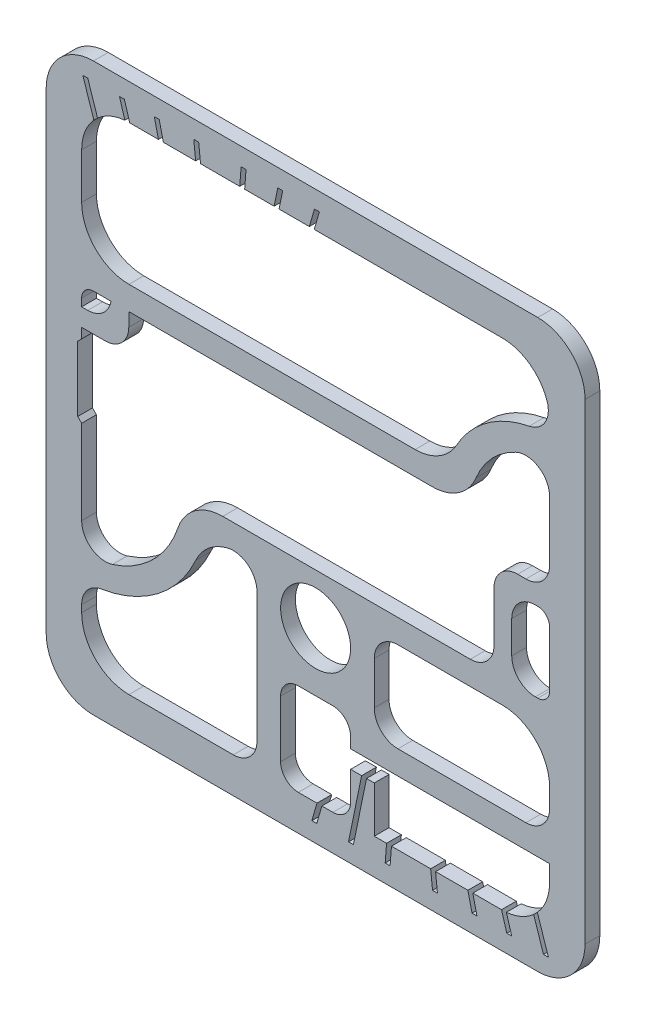
SolidWorks part; units mm, degrees
ref_plane "Front Plane" through (0, 0, 0) normal (0, 0, 1) x (1, 0, 0)
ref_plane "Top Plane" through (0, 0, 0) normal (0, 1, 0) x (1, 0, 0)
ref_plane "Right Plane" through (0, 0, 0) normal (1, 0, 0) x (0, 0, -1)
sketch "Sketch1" plane through (0, 0, 0) normal (0, 0, 1) x (1, 0, 0)
  line L0 (44.642, 22.5192) -> (44.642, 18.7092) construction
  line L1 (-8.1388, 22.5192) -> (49.7286, 22.5192)
  line L2 (-8.1388, 22.5192) -> (-8.1388, -38.311)
  line L3 (-8.1388, -38.311) -> (49.7286, -38.311)
  line L4 (49.7286, 22.5192) -> (49.7286, -38.311)
  line L5 (45.9186, -34.501) -> (-4.3288, -34.501)
  line L6 (45.9186, -34.501) -> (45.9186, 18.7092)
  line L7 (45.9186, 18.7092) -> (-4.3288, 18.7092)
  line L8 (-4.3288, -34.501) -> (-4.3288, 18.7092)
  line L9 (44.642, 20.6142) -> (-35.1587, 20.6142) construction
  line L10 (-4.3288, -31.0517) -> (-8.1388, -31.0517) construction
  line L11 (-6.2338, -31.0517) -> (-6.2338, 6.9585) construction
  line L12 (20.6696, 20.6142) -> (21.1982, 20.6142) construction
  line L13 (-6.2338, -12.887) -> (-6.2338, -25.1298) construction
  line L14 (3.0779, -34.501) -> (3.0779, -38.311) construction
  line L15 (3.0779, -36.406) -> (37.3423, -36.406) construction
  line L17 (49.7286, 15.2205) -> (45.9186, 15.2205) construction
  line L18 (47.8236, 15.2205) -> (47.8236, -0.9437) construction
  line L19 (47.8236, -2.9048) -> (47.8236, 9.338) construction
  line L20 (20.9203, -36.406) -> (20.3916, -36.406) construction
  dimension "D1" = 3.81
  dimension "D2" = 3.81
extrude "Boss-Extrude1" add sketch "Sketch1" along normal blind 1.5875
sketch "Sketch2" plane through (0, 0, 0) normal (0, 0, -1) x (-1, 0, 0)
  line L0 (-45.9186, -34.501) -> (-45.9186, 18.7092) construction
  line L1 (-34.8696, 3.653) -> (4.3288, 3.653)
  line L2 (-45.9186, 3.653) -> (-45.9186, 0.7339)
  line L3 (-37.4096, 1.113) -> (4.3288, 1.113)
  line L4 (4.3288, 3.653) -> (4.3288, 1.113)
  line L5 (4.3288, 18.7092) -> (4.3288, -34.501) construction
  line L6 (-33.4496, 1.113) -> (-36.4496, 1.113) construction
  line L7 (1.2504, -12.887) -> (-36.4496, -12.887) construction
  line L8 (-45.9186, -15.427) -> (-8.8785, -15.427)
  line L9 (-45.9186, -15.427) -> (-45.9186, -12.887)
  line L10 (-45.9186, -12.887) -> (-6.5805, -12.887)
  line L11 (1.357, -21.2563) -> (14.2432, -21.2563) construction
  line L12 (4.3288, -23.7963) -> (4.3288, -26.3363)
  line L13 (-45.9186, 12.162) -> (-45.9186, 9.622)
  arc A0 (-45.9186, 9.622) -> (-37.4096, 1.113) centre (-45.9186, 1.113) cw
  arc A1 (-45.9186, 12.162) -> (-34.8696, 3.653) centre (-45.9186, 0.7339) cw
  arc A2 (4.3288, -23.7963) -> (-6.5805, -12.887) centre (4.3288, -12.887) cw
  arc A3 (-8.8785, -15.427) -> (4.3288, -26.3363) centre (4.3288, -12.887) ccw
  circle A5 centre (1.357, -18.2591) radius 2.9972 construction
  line M5 (-45.9186, -34.501) -> (-45.9186, 18.7092)
  line M7 (4.3288, 18.7092) -> (4.3288, -34.501)
  dimension "D5" = 2.54
  dimension "D1" = 2.54
  dimension "D2" = 2.54
  dimension "D3" = 2.54
  dimension "D4" = 2.54
  dimension "D6" = 2.54
  dimension "D7" = 2.54
extrude "Boss-Extrude2" add sketch "Sketch2" against normal up to surface (1.5875 mm away) contours A1 A0 L3 L1 M5 M7 | L10 L8 M5 M7 region at (15.2704, 3.1385, 0) region at (-3.8086, -25.0663, 0) up to face at (20.7949, -7.8959, 1.5875)
sketch "Sketch3" plane through (0, 0, 0) normal (0, 0, -1) x (-1, 0, 0)
  line L0 (-45.9186, -2.4349) -> (-39.9496, -2.4349)
  line L1 (-45.9186, -12.887) -> (-45.9186, 9.622) construction
  line L2 (-39.9496, -4.387) -> (-39.9496, -11.387) construction
  line L3 (-39.9496, -2.4349) -> (-39.9496, -12.887)
  line L4 (-45.9186, -12.887) -> (-6.5805, -12.887) construction
  line L5 (-39.9496, -12.887) -> (-41.8546, -12.887)
  line L6 (-41.8546, -12.887) -> (-41.8546, -4.3399)
  line L7 (-41.8546, -4.3399) -> (-45.9186, -4.3399)
  line L8 (-45.9186, -4.3399) -> (-45.9186, -2.4349)
  line L9 (-42.9468, -0.5299) -> (-53.4831, -0.5299) construction
  line L10 (-0.7296, 1.113) -> (-0.7296, -2.887)
  line L11 (-37.4096, 1.113) -> (4.3288, 1.113) construction
  line L12 (-1.9996, -2.887) -> (1.2504, -2.887) construction
  line L13 (-0.7296, -2.887) -> (4.3288, -2.887)
  line L14 (4.3288, 1.113) -> (4.3288, -23.7963) construction
  line L15 (4.3288, -2.887) -> (4.3288, -0.982)
  line L16 (4.3288, -0.982) -> (1.1754, -0.982)
  line L17 (1.1754, -0.982) -> (1.1754, 1.113)
  line L18 (1.1754, 1.113) -> (-0.7296, 1.113)
  circle A0 centre (-42.9468, 2.4673) radius 2.9972 construction
  dimension "D1" = 1.905
  dimension "D2" = 1.905
  dimension "D3" = 1.905
  dimension "D4" = 1.905
  dimension "D5" = 1.27
  dimension "D6" = 1.905
extrude "Boss-Extrude3" add sketch "Sketch3" against normal up to surface (1.5875 mm away) up to face at (21.2778, -6.3699, 1.5875)
fillet "Fillet1" radius 5.08 4 edges at (49.7286, -38.311, 0.7937) (-8.1388, -38.311, 0.7937) (-8.1388, 22.5192, 0.7937) (49.7286, 22.5192, 0.7937)
fillet "Fillet2" radius 5.08 10 edges at (8.8785, -15.427, 0.7937) (45.9186, -15.427, 0.7937) (45.9186, -34.501, 0.7937) (-4.3288, -34.501, 0.7937) (34.8696, 3.653, 0.7937) (-4.3288, 3.653, 0.7937) (45.9186, 18.7092, 0.7937) (-4.3288, 18.7092, 0.7937) (6.5805, -12.887, 0.7937) (37.4096, 1.113, 0.7937)
fillet "Fillet3" radius 2.54 11 edges at (41.8546, -4.3399, 0.7938) (39.9496, -12.887, 0.7938) (41.8546, -12.887, 0.7938) (39.9496, -2.4349, 0.7938) (45.9186, -2.4349, 0.7938) (-1.1754, -0.982, 0.7938) (0.7296, -2.887, 0.7938) (45.9186, 9.622, 0.7937) (-4.3288, -26.3363, 0.7937) (-4.3288, -23.7963, 0.7937) (45.9186, 12.162, 0.7937)
fillet "Fillet4" radius 1.27 3 edges at (45.9186, -12.887, 0.7937) (45.9186, -4.3399, 0.7938) (-4.3288, 1.113, 0.7937)
sketch "Sketch5" plane through (0, 0, 0) normal (0, 0, -1) x (-1, 0, 0)
  line L0 (-40.8386, -15.427) -> (-12.5612, -15.427) construction
  line L1 (-27.0941, -15.427) -> (-14.4957, -15.427)
  line L2 (-27.0941, -15.427) -> (-27.0941, -34.501)
  line L3 (-27.0941, -34.501) -> (-14.4957, -34.501)
  line L4 (-14.4957, -15.427) -> (-14.4957, -34.501)
  line L5 (-0.7512, -34.501) -> (-40.8386, -34.501) construction
  line L6 (-24.5541, -18.2972) -> (-27.0941, -18.2972) construction
  line L9 (-17.0357, -18.2972) -> (-14.4957, -18.2972) construction
  circle A1 centre (-20.7949, -18.2972) radius 3.7592 construction
  dimension "D1" = 2.54
extrude "Boss-Extrude4" add sketch "Sketch5" against normal up to surface (1.5875 mm away) up to face at (-3.29, -0.0173, 1.5875)
sketch "Sketch6" plane through (0, 0, 0) normal (0, 0, -1) x (-1, 0, 0)
  circle A0 centre (-20.7949, -18.2972) radius 3.7592 construction
  circle A1 centre (-20.7949, -18.2972) radius 3.7592
extrude "Cut-Extrude2" cut sketch "Sketch6" against normal up to surface (1.5875 mm away) up to face at (4.8008, -25.4732, 1.5875)
sketch "Sketch7" plane through (0, 0, 0) normal (0, 0, -1) x (-1, 0, 0)
  line L0 (-27.0941, -15.427) -> (-27.0941, -34.501) construction
  line L1 (-24.5541, -24.5964) -> (-17.0357, -24.5964)
  line L2 (-24.5541, -24.5964) -> (-24.5541, -34.501)
  line L3 (-24.5541, -34.501) -> (-17.0357, -34.501)
  line L4 (-17.0357, -24.5964) -> (-17.0357, -34.501)
  line L5 (-14.4957, -34.501) -> (-14.4957, -15.427) construction
  line L6 (-0.7512, -34.501) -> (-14.4957, -34.501) construction
  line L7 (-20.7949, -22.0564) -> (-6.5424, -22.0564) construction
  line L8 (-20.7949, -22.0564) -> (-20.7949, -21.3452) construction
  circle A0 centre (-20.7949, -18.2972) radius 3.7592 construction
  dimension "D1" = 2.54
  dimension "D2" = 2.54
  dimension "D3" = 2.54
extrude "Cut-Extrude3" cut sketch "Sketch7" against normal up to surface (1.5875 mm away) up to face at (24.5541, -18.2972, 1.5875)
fillet "Fillet5" radius 1.905 4 edges at (24.5541, -34.501, 0.7937) (17.0357, -34.501, 0.7938) (17.0357, -24.5964, 0.7938) (24.5541, -24.5964, 0.7938)
sketch "Sketch8" plane through (0, 0, 0) normal (0, 0, -1) x (-1, 0, 0)
  line L0 (-45.9186, -29.421) -> (-45.9186, -20.507) construction
  line L1 (-45.9186, -25.103) -> (-27.0941, -25.103)
  line L2 (-45.9186, -25.103) -> (-45.9186, -27.643)
  line L3 (-45.9186, -27.643) -> (-27.0941, -27.643)
  line L4 (-27.0941, -25.103) -> (-27.0941, -27.643)
  line L5 (-27.0941, -15.427) -> (-27.0941, -34.501) construction
  line L6 (-45.7916, -27.643) -> (-20.3916, -27.643) construction
  dimension "D1" = 2.54
extrude "Boss-Extrude5" add sketch "Sketch8" against normal up to surface (1.5875 mm away) up to face at (20.7949, -29.5487, 1.5875)
fillet "Fillet6" radius 2.54 5 edges at (27.0941, -15.427, 0.7937) (14.4957, -15.427, 0.7937) (14.4957, -34.501, 0.7937) (27.0941, -25.103, 0.7937) (45.9186, -25.103, 0.7937)
sketch "Sketch4" plane through (0, 0, 0) normal (0, 0, -1) x (-1, 0, 0)
  line L0 (3.2504, -2.887) -> (4.7504, -4.387) construction
  line L1 (4.7504, -11.387) -> (3.2504, -12.887) construction
  line L2 (3.2504, -2.887) -> (4.7504, -4.387)
  line L3 (4.7504, -11.387) -> (3.2504, -12.887)
  line L4 (4.7504, -4.387) -> (4.7504, -11.387) construction
  line L5 (4.7504, -4.387) -> (4.7504, -11.387)
  line L6 (3.2504, -2.887) -> (3.2504, -12.887)
  line L32 (4.2018, 11.8512) -> (4.2018, 13.7562)
  line L33 (4.2018, 13.7562) -> (1.9364, 13.7562)
  line L34 (1.9364, 13.7562) -> (4.2018, 20.6142)
  line L35 (4.2018, 20.6142) -> (3.6731, 20.6142)
  line L36 (3.6731, 20.6142) -> (1.4078, 13.7562)
  line L37 (1.4078, 13.7562) -> (-1.7768, 13.7562)
  line L38 (-1.7768, 13.7562) -> (0.2648, 20.6142)
  line L39 (0.2648, 20.6142) -> (-0.2639, 20.6142)
  line L40 (-0.2639, 20.6142) -> (-2.3054, 13.7562)
  line L41 (-2.3054, 13.7562) -> (-5.0788, 13.7562)
  line L42 (-5.0788, 13.7562) -> (-3.469, 20.6142)
  line L43 (-3.469, 20.6142) -> (-3.9977, 20.6142)
  line L44 (-3.9977, 20.6142) -> (-5.6074, 13.7562)
  line L45 (-5.6074, 13.7562) -> (-8.4316, 13.7562)
  line L46 (-8.4316, 13.7562) -> (-7.7108, 20.6142)
  line L47 (-7.7108, 20.6142) -> (-8.2395, 20.6142)
  line L48 (-8.2395, 20.6142) -> (-8.9602, 13.7562)
  line L49 (-8.9602, 13.7562) -> (-12.267, 13.7562)
  line L50 (-12.267, 13.7562) -> (-12.7956, 20.6142)
  line L51 (-12.7956, 20.6142) -> (-13.3242, 20.6142)
  line L52 (-13.3242, 20.6142) -> (-12.7956, 13.7562)
  line L53 (-12.7956, 13.7562) -> (-15.3277, 13.7562)
  line L54 (-15.3277, 13.7562) -> (-16.7326, 20.6142)
  line L55 (-16.7326, 20.6142) -> (-17.2612, 20.6142)
  line L56 (-17.2612, 20.6142) -> (-15.8563, 13.7562)
  line L57 (-15.8563, 13.7562) -> (-18.6963, 13.7562)
  line L58 (-18.6963, 13.7562) -> (-20.6696, 20.6142)
  line L59 (-20.6696, 20.6142) -> (-21.1982, 20.6142)
  line L60 (-21.1982, 20.6142) -> (-19.225, 13.7562)
  line L61 (-19.225, 13.7562) -> (-21.1982, 13.7562)
  line L62 (-21.1982, 13.7562) -> (-21.1982, 11.8512)
  line L63 (-21.1982, 11.8512) -> (4.2018, 11.8512)
  line L64 (4.2018, 11.8512) -> (4.2018, 13.7562)
  line L65 (4.2018, 13.7562) -> (1.9364, 13.7562)
  line L66 (1.9364, 13.7562) -> (4.2018, 20.6142)
  line L67 (4.2018, 20.6142) -> (3.6731, 20.6142)
  line L68 (3.6731, 20.6142) -> (1.4078, 13.7562)
  line L69 (1.4078, 13.7562) -> (-1.7768, 13.7562)
  line L70 (-1.7768, 13.7562) -> (0.2648, 20.6142)
  line L71 (0.2648, 20.6142) -> (-0.2639, 20.6142)
  line L72 (-0.2639, 20.6142) -> (-2.3054, 13.7562)
  line L73 (-2.3054, 13.7562) -> (-5.0788, 13.7562)
  line L74 (-5.0788, 13.7562) -> (-3.469, 20.6142)
  line L75 (-3.469, 20.6142) -> (-3.9977, 20.6142)
  line L76 (-3.9977, 20.6142) -> (-5.6074, 13.7562)
  line L77 (-5.6074, 13.7562) -> (-8.4316, 13.7562)
  line L78 (-8.4316, 13.7562) -> (-7.7108, 20.6142)
  line L79 (-7.7108, 20.6142) -> (-8.2395, 20.6142)
  line L80 (-8.2395, 20.6142) -> (-8.9602, 13.7562)
  line L81 (-8.9602, 13.7562) -> (-12.267, 13.7562)
  line L82 (-12.267, 13.7562) -> (-12.7956, 20.6142)
  line L83 (-12.7956, 20.6142) -> (-13.3242, 20.6142)
  line L84 (-13.3242, 20.6142) -> (-12.7956, 13.7562)
  line L85 (-12.7956, 13.7562) -> (-15.3277, 13.7562)
  line L86 (-15.3277, 13.7562) -> (-16.7326, 20.6142)
  line L87 (-16.7326, 20.6142) -> (-17.2612, 20.6142)
  line L88 (-17.2612, 20.6142) -> (-15.8563, 13.7562)
  line L89 (-15.8563, 13.7562) -> (-18.6963, 13.7562)
  line L90 (-18.6963, 13.7562) -> (-20.6696, 20.6142)
  line L91 (-20.6696, 20.6142) -> (-21.1982, 20.6142)
  line L92 (-21.1982, 20.6142) -> (-19.225, 13.7562)
  line L93 (-19.225, 13.7562) -> (-21.1982, 13.7562)
  line L94 (-21.1982, 13.7562) -> (-21.1982, 11.8512)
  line L95 (-21.1982, 11.8512) -> (4.2018, 11.8512)
  line L96 (-45.7916, -27.643) -> (-45.7916, -29.548)
  line L97 (-45.7916, -29.548) -> (-43.5263, -29.548)
  line L98 (-43.5263, -29.548) -> (-45.7916, -36.406)
  line L99 (-45.7916, -36.406) -> (-45.263, -36.406)
  line L100 (-45.263, -36.406) -> (-42.9976, -29.548)
  line L101 (-42.9976, -29.548) -> (-39.8131, -29.548)
  line L102 (-39.8131, -29.548) -> (-41.8546, -36.406)
  line L103 (-41.8546, -36.406) -> (-41.326, -36.406)
  line L104 (-41.326, -36.406) -> (-39.2845, -29.548)
  line L105 (-39.2845, -29.548) -> (-36.5111, -29.548)
  line L106 (-36.5111, -29.548) -> (-38.1208, -36.406)
  line L107 (-38.1208, -36.406) -> (-37.5922, -36.406)
  line L108 (-37.5922, -36.406) -> (-35.9825, -29.548)
  line L109 (-35.9825, -29.548) -> (-33.1583, -29.548)
  line L110 (-33.1583, -29.548) -> (-33.879, -36.406)
  line L111 (-33.879, -36.406) -> (-33.3504, -36.406)
  line L112 (-33.3504, -36.406) -> (-32.6297, -29.548)
  line L113 (-32.6297, -29.548) -> (-29.3229, -29.548)
  line L114 (-29.3229, -29.548) -> (-28.7943, -36.406)
  line L115 (-28.7943, -36.406) -> (-28.2656, -36.406)
  line L116 (-28.2656, -36.406) -> (-28.7943, -29.548)
  line L117 (-28.7943, -29.548) -> (-26.2622, -29.548)
  line L118 (-26.2622, -29.548) -> (-24.8573, -36.406)
  line L119 (-24.8573, -36.406) -> (-24.3286, -36.406)
  line L120 (-24.3286, -36.406) -> (-25.7336, -29.548)
  line L121 (-25.7336, -29.548) -> (-22.8935, -29.548)
  line L122 (-22.8935, -29.548) -> (-20.9203, -36.406)
  line L123 (-20.9203, -36.406) -> (-20.3916, -36.406)
  line L124 (-20.3916, -36.406) -> (-22.3649, -29.548)
  line L125 (-22.3649, -29.548) -> (-20.3916, -29.548)
  line L126 (-20.3916, -29.548) -> (-20.3916, -27.643)
  line L127 (-20.3916, -27.643) -> (-45.7916, -27.643)
  line L128 (-45.7916, -27.643) -> (-45.7916, -29.548)
  line L129 (-45.7916, -29.548) -> (-43.5263, -29.548)
  line L130 (-43.5263, -29.548) -> (-45.7916, -36.406)
  line L131 (-45.7916, -36.406) -> (-45.263, -36.406)
  line L132 (-45.263, -36.406) -> (-42.9976, -29.548)
  line L133 (-42.9976, -29.548) -> (-39.8131, -29.548)
  line L134 (-39.8131, -29.548) -> (-41.8546, -36.406)
  line L135 (-41.8546, -36.406) -> (-41.326, -36.406)
  line L136 (-41.326, -36.406) -> (-39.2845, -29.548)
  line L137 (-39.2845, -29.548) -> (-36.5111, -29.548)
  line L138 (-36.5111, -29.548) -> (-38.1208, -36.406)
  line L139 (-38.1208, -36.406) -> (-37.5922, -36.406)
  line L140 (-37.5922, -36.406) -> (-35.9825, -29.548)
  line L141 (-35.9825, -29.548) -> (-33.1583, -29.548)
  line L142 (-33.1583, -29.548) -> (-33.879, -36.406)
  line L143 (-33.879, -36.406) -> (-33.3504, -36.406)
  line L144 (-33.3504, -36.406) -> (-32.6297, -29.548)
  line L145 (-32.6297, -29.548) -> (-29.3229, -29.548)
  line L146 (-29.3229, -29.548) -> (-28.7943, -36.406)
  line L147 (-28.7943, -36.406) -> (-28.2656, -36.406)
  line L148 (-28.2656, -36.406) -> (-28.7943, -29.548)
  line L149 (-28.7943, -29.548) -> (-26.2622, -29.548)
  line L150 (-26.2622, -29.548) -> (-24.8573, -36.406)
  line L151 (-24.8573, -36.406) -> (-24.3286, -36.406)
  line L152 (-24.3286, -36.406) -> (-25.7336, -29.548)
  line L153 (-25.7336, -29.548) -> (-22.8935, -29.548)
  line L154 (-22.8935, -29.548) -> (-20.9203, -36.406)
  line L155 (-20.9203, -36.406) -> (-20.3916, -36.406)
  line L156 (-20.3916, -36.406) -> (-22.3649, -29.548)
  line L157 (-22.3649, -29.548) -> (-20.3916, -29.548)
  line L158 (-20.3916, -29.548) -> (-20.3916, -27.643)
  line L159 (-20.3916, -27.643) -> (-45.7916, -27.643)
  dimension "D1" = 0
  dimension "D2" = 0
extrude "Cut-Extrude1" cut sketch "Sketch4" against normal up to surface (1.5875 mm away) up to face at (37.5833, -30.9522, 1.5875)
